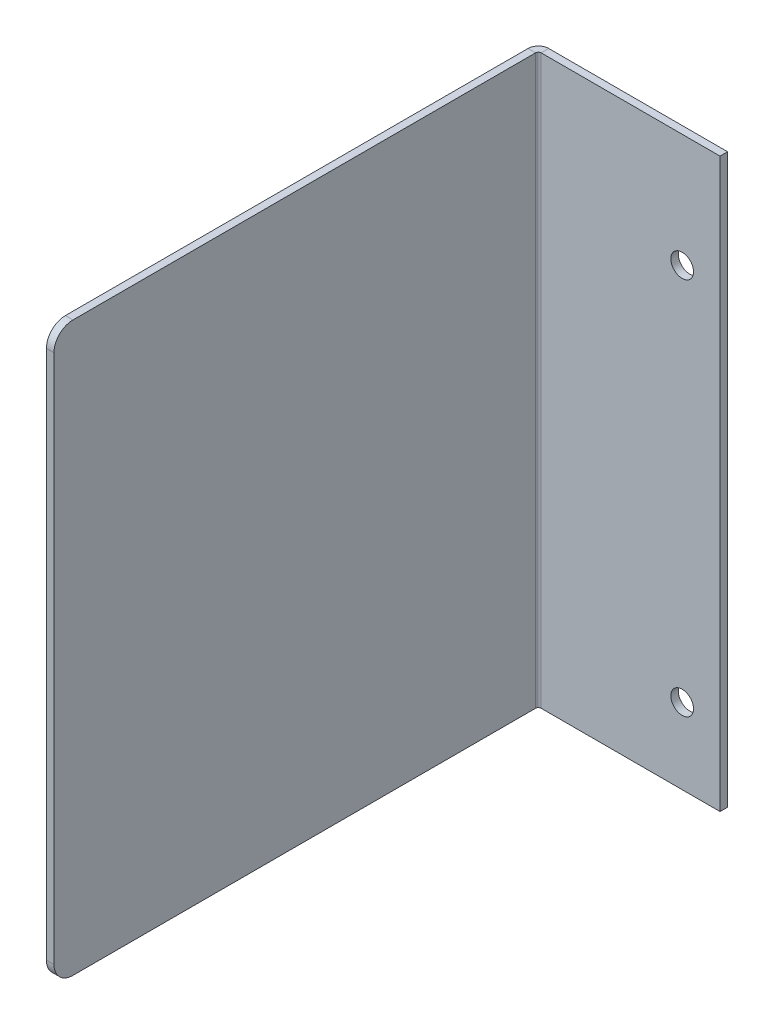
SolidWorks part; units mm, degrees
note: The reader was unsure of these and kept them because the rebuilt part matched: flange length of "边线-法兰1".
ref_plane "前视基准面" through (0, 0, 0) normal (0, 0, 1) x (1, 0, 0)
ref_plane "上视基准面" through (0, 0, 0) normal (0, 1, 0) x (1, 0, 0)
ref_plane "右视基准面" through (0, 0, 0) normal (1, 0, 0) x (0, 0, -1)
sketch "草图1" plane through (0, 0, 0) normal (0, 0, 1) x (1, 0, 0)
  line L1 (-8.3376, 7.7494) -> (41.6624, 7.7494)
  line L2 (-8.3376, 7.7494) -> (-8.3376, -142.2506)
  line L3 (-8.3376, -142.2506) -> (41.6624, -142.2506)
  line L4 (41.6624, 7.7494) -> (41.6624, -142.2506)
  dimension "D1" = 50
  dimension "D2" = 150
sheet metal parameters "钣金1" thickness 2 parameters "D1"=0.7366
base flange "基体-法兰1" sketch "草图1" thickness 2 reverse thickness direction no parameters "D1"=0.7366
ref_plane "基准面4" through (-8.3376, 7.7494, 0) normal (0, -1, 0) x (-1, 0, 0)
edge flange "边线-法兰1" sketch "草图7" flange angle 90 flange length 130 flange position material inside bend radius 0.7366 thickness 2 relief rectangular parameters "D6"=10
sketch "草图7" plane through (-8.3376, 0, 0) normal (-1, 0, 0) x (0, -1, 0)
  line L2 (-7.7494, 0) -> (-7.7494, 128)
  line L3 (-7.7494, 128) -> (142.2506, 128)
  line L4 (142.2506, 128) -> (142.2506, 0)
  line L7 (-7.7494, 0) -> (142.2506, 0) construction
  line L8 (-7.7494, 0) -> (142.2506, 0)
bend "边线折弯1" bend radius 0.7366 bend angle 90 parameters "D5"=1
sketch "草图8" plane through (0, 0, 0) normal (0, 0, 1) x (1, 0, 0)
  line L0 (41.6624, 7.7494) -> (-5.601, 7.7494) construction
  line L1 (41.6624, -142.2506) -> (41.6624, 7.7494) construction
  circle A0 centre (31.6624, -22.2506) radius 3
  dimension "D1" = 30
  dimension "D2" = 10
extrude "切除-拉伸1" cut sketch "草图8" against normal blind 10 normal cut yes
pattern_linear "阵列(线性)1" count 2 spacing 100 along (0, -1, 0) of "切除-拉伸1"
fillet "圆角2" radius 5 1 edges at (-7.3376, 7.7494, 128)
fillet "圆角3" radius 5 1 edges at (-7.3376, -142.2506, 128)
flat pattern "平板型式1" [suppressed]
sketch "折弯-线1" plane through (0, 0, 0) normal (0, 0, 1) x (1, 0, 0)
  line L0 (-6.9649, 7.7494) -> (-6.9649, -142.2506) construction
  line L1 (-6.9649, 7.7494) -> (-6.9649, -142.2506) construction
sketch3d "边界框1" [suppressed]
  line L0 (-135.5922, 7.7494, 0) -> (41.6624, 7.7494, 0) construction
  line L1 (-135.5922, -142.2506, 0) -> (41.6624, -142.2506, 0) construction
  line L2 (-135.5922, 7.7494, 0) -> (-135.5922, -142.2506, 0) construction
  line L3 (41.6624, 7.7494, 0) -> (41.6624, -142.2506, 0) construction
bend of the flat pattern "展平-<边线折弯1>1"
